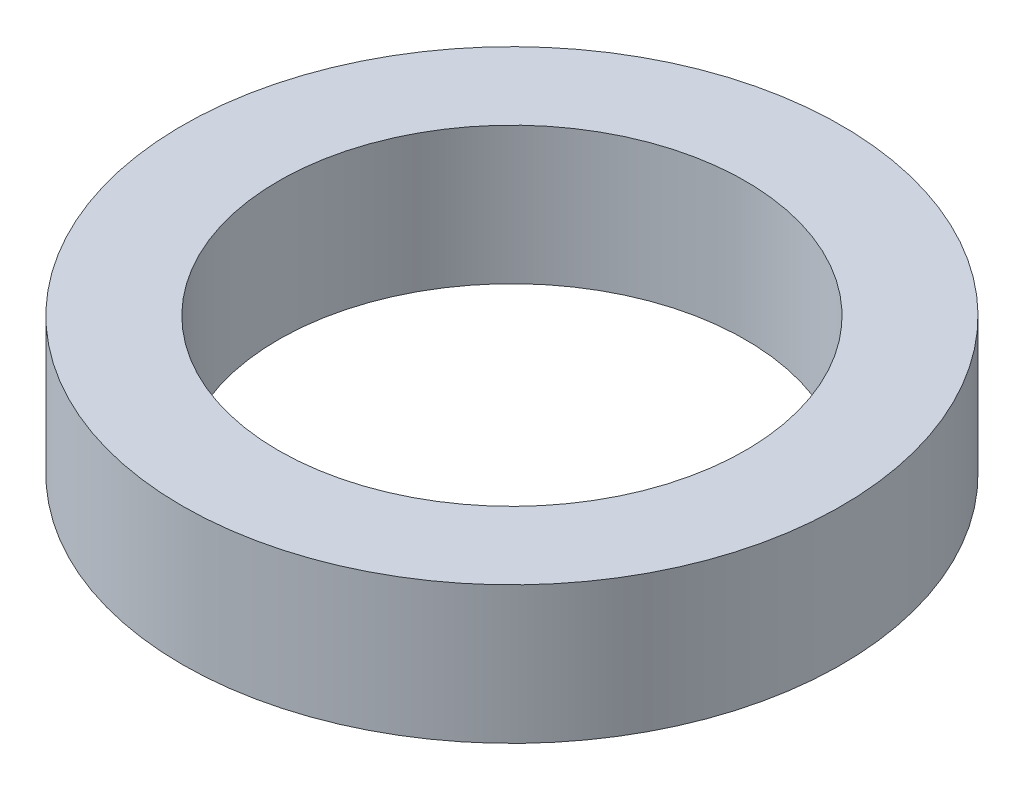
SolidWorks part; units mm, degrees
ref_plane "Front Plane" through (0, 0, 0) normal (0, 0, 1) x (1, 0, 0)
ref_plane "Top Plane" through (0, 0, 0) normal (0, 1, 0) x (1, 0, 0)
ref_plane "Right Plane" through (0, 0, 0) normal (1, 0, 0) x (0, 0, -1)
sketch "Sketch1" plane through (0, 0, 0) normal (0, 1, 0) x (1, 0, 0)
  circle A0 centre (0, 0) radius 60
  dimension "FLANGE_OD" = 120
extrude "Boss-Extrude1" add sketch "Sketch1" along normal blind 25
sketch "Sketch2" plane through (0, 0, 0) normal (0, 1, 0) x (1, 0, 0)
  circle A0 centre (0, 0) radius 42.5
  dimension "BORE_D" = 85
extrude "Cut-Extrude1" cut sketch "Sketch2" along normal through all
sketch "Sketch3" plane through (0, 25, 0) normal (0, 1, 0) x (1, 0, 0)
  circle A0 centre (0, 0) radius 23.8825 construction
  circle A1 centre (-23.8825, 0) radius 2.1555
  dimension "BOLT_D" = 4.3111
  dimension "BOLT_PCD" = 47.7649
extrude "Cut-Extrude2" cut sketch "Sketch3" against normal blind 15.6275 rebuild error yes
pattern_circular "CirPattern1" count 6 over 360 rebuild error yes
